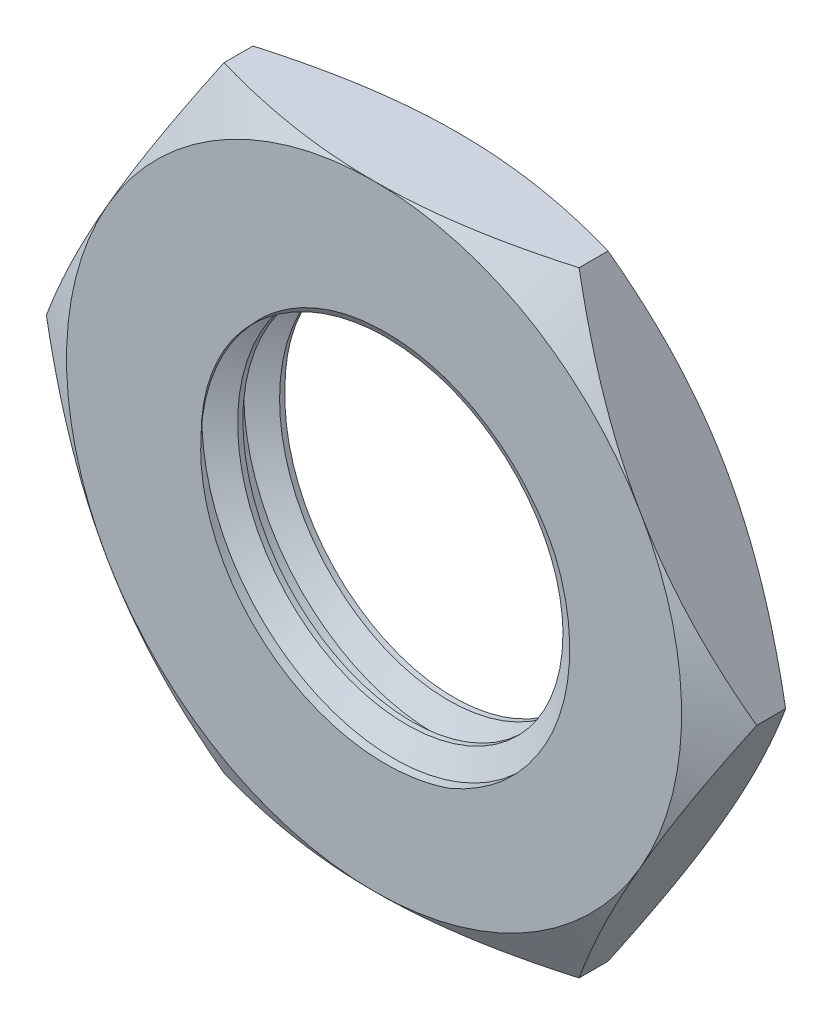
SolidWorks part; units mm, degrees
ref_plane "Plan de face" through (0, 0, 0) normal (0, 0, 1) x (1, 0, 0)
ref_plane "Plan de dessus" through (0, 0, 0) normal (0, 1, 0) x (1, 0, 0)
ref_plane "Plan de droite" through (0, 0, 0) normal (1, 0, 0) x (0, 0, -1)
sketch "Contour_écrou_M14" plane through (0, 0, 0) normal (0, 0, 1) x (1, 0, 0)
  line L1 (12.7017, 0) -> (6.3509, 11)
  line L2 (6.3509, 11) -> (-6.3509, 11)
  line L3 (-6.3509, 11) -> (-12.7017, 0)
  line L4 (-12.7017, 0) -> (-6.3509, -11)
  line L5 (-6.3509, -11) -> (6.3509, -11)
  line L6 (6.3509, -11) -> (12.7017, 0)
  circle A0 centre (0, 0) radius 11 construction
  dimension "D1" = 22
extrude "Boss.-Extru.1_Contour_écrou_M14" add sketch "Contour_écrou_M14" along normal mid plane 3
sketch "Tap_Drill_Hole" plane through (0, 0, -1.5) normal (0, 0, -1) x (-1, 0, 0)
  circle A0 centre (0, 0) radius 6.188
  dimension "D1" = 12.376
extrude "Enlèv. mat.-Extru.2_Tap_Drill_Hole" cut sketch "Tap_Drill_Hole" against normal up to next
ref_axis "Axe1_central" through (0, 0, -2.3899) along (0, 0, 1)
sketch "Coins ronds" plane through (0, 0, -1.5) normal (0, 0, -1) x (-1, 0, 0)
  line L0 (6.3509, 11) -> (12.7017, 0) construction
  circle A0 centre (0, 0) radius 11
extrude "Enlèv. mat.-Extru.1_Coins ronds" cut sketch "Coins ronds" against normal blind 10 draft 60 flip side to cut
mirror "Symétrie1_Coins ronds" about plane through (0, 0, 0) normal (0, 0, 1) of "Enlèv. mat.-Extru.1_Coins ronds"
sketch "Esquisse4" plane through (0, 0, -1.5) normal (0, 0, -1) x (-1, 0, 0)
  circle A0 centre (0, 0) radius 6.75
curve "Hélice/Spirale1" pitch 1.5 height 7.5 radius 6.75 centre (0, 0, -1.5) axis (0, 0, 1) start towards (-1, 0, 0)
sketch "Dents" plane through (0, 0, 0) normal (0, 1, 0) x (1, 0, 0)
  line L0 (-6.188, 2.8126) -> (-6.188, 1.5)
  line L1 (-6.188, 1.5) -> (-7, 1.9688)
  line L2 (-7.3248, 2.1563) -> (-7, 2.3438) construction
  line L3 (-6.188, 1.5) -> (-6.188, -1.5) construction
  line L4 (-7, 2.3438) -> (-7, 1.9688)
  line L5 (-7, 2.3438) -> (-6.188, 2.8126)
  line L6 (-7, 1.9688) -> (-7.3248, 2.1563) construction
  line L7 (0, 1.5) -> (-9.5263, 1.5) construction
  dimension "D1" = 60
  dimension "D2" = 0.812
  dimension "D3" = 0.375
sweep "Enlèvement de matière-Balayage1" cut profiles "Dents" path "Hélice/Spirale1" align with end faces yes
